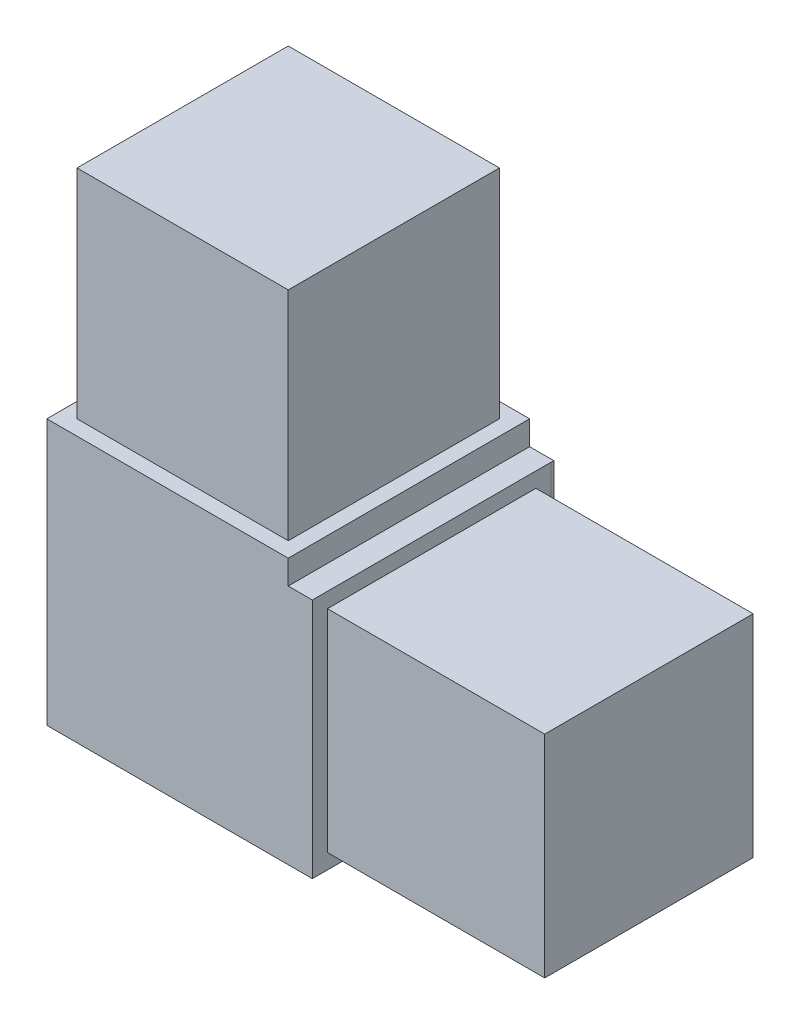
SolidWorks part; units mm, degrees
material "ALUMINUM 6061-T6"
ref_plane "Front Plane" through (0, 0, 0) normal (0, 0, 1) x (1, 0, 0)
ref_plane "Top Plane" through (0, 0, 0) normal (0, 1, 0) x (1, 0, 0)
ref_plane "Right Plane" through (0, 0, 0) normal (1, 0, 0) x (0, 0, -1)
sketch "Sketch1" plane through (0, 0, 0) normal (0, 0, 1) x (1, 0, 0)
  line L1 (-25.4, -25.4) -> (25.4, -25.4)
  line L2 (-25.4, -25.4) -> (-25.4, 25.4)
  line L3 (-25.4, 25.4) -> (25.4, 25.4)
  line L4 (25.4, -25.4) -> (25.4, 25.4)
  line L5 (-25.4, -25.4) -> (25.4, 25.4) construction
  line L6 (-25.4, 25.4) -> (25.4, -25.4) construction
  point P0 (0, 0)
  dimension "D1" = 50.8
  dimension "D2" = 50.8
extrude "Boss-Extrude1" add sketch "Sketch1" along normal mid plane 25.4
sketch "Sketch2" plane through (0, 0, 12.7) normal (0, 0, 1) x (1, 0, 0)
  line L1 (25.4, 25.4) -> (0, 25.4)
  line L2 (25.4, 25.4) -> (25.4, 0)
  line L3 (25.4, 0) -> (0, 0)
  line L4 (0, 25.4) -> (0, 0)
extrude "Cut-Extrude1" cut sketch "Sketch2" against normal through all
sketch "Sketch3" plane through (25.4, 0, 0) normal (1, 0, 0) x (0, 0, -1)
  line L0 (12.7, 0) -> (-12.7, 0) construction
  line L1 (-12.7, -25.4) -> (12.4098, -25.4)
  line L2 (-12.7, -25.4) -> (-12.7, 0)
  line L3 (-12.7, 0) -> (12.4098, 0)
  line L4 (12.4098, -25.4) -> (12.4098, 0)
  line L5 (-11.1125, -23.8125) -> (-11.1125, -1.5875)
  line L6 (-11.1125, -1.5875) -> (10.8223, -1.5875)
  line L7 (10.8223, -23.8125) -> (10.8223, -1.5875)
  line L8 (-11.1125, -23.8125) -> (10.8223, -23.8125)
  dimension "D1" = 1.5875
extrude "Cut-Extrude2" cut sketch "Sketch3" against normal blind 22.86
sketch "Sketch5" plane through (0, 25.4, 0) normal (0, 1, 0) x (1, 0, 0)
  line L0 (-1.5875, 11.1125) -> (-23.8125, 11.1125)
  line L1 (0, -12.7) -> (-25.4, -12.7)
  line L2 (0, -12.7) -> (0, 12.7)
  line L3 (0, 12.7) -> (-25.4, 12.7)
  line L4 (-25.4, -12.7) -> (-25.4, 12.7)
  line L5 (-23.8125, -11.1125) -> (-23.8125, 11.1125)
  line L6 (-1.5875, -11.1125) -> (-23.8125, -11.1125)
  line L7 (-1.5875, -11.1125) -> (-1.5875, 11.1125)
  point P4 (-3.4197, 4.7842)
  dimension "D1" = 1.5875
extrude "Cut-Extrude4" cut sketch "Sketch5" against normal blind 22.86
sketch "Sketch6" plane through (0, 0, -12.7) normal (0, 0, -1) x (-1, 0, 0)
  line L0 (0, 0) -> (-25.4, 0) construction
  line L1 (-25.4, -25.4) -> (-2.5647, -25.4)
  line L2 (-25.4, -25.4) -> (-25.4, 0)
  line L3 (-25.4, 0) -> (-2.5647, 0)
  line L4 (-2.5647, -25.4) -> (-2.5647, 0)
extrude "Cut-Extrude5" cut sketch "Sketch6" against normal up to body
